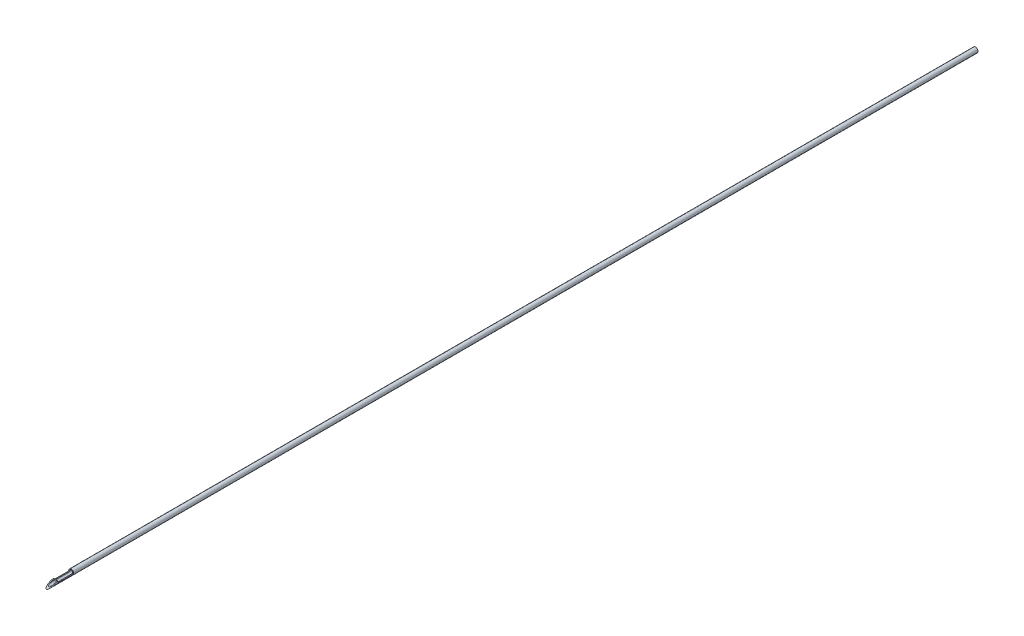
SolidWorks part; units mm, degrees
ref_plane "Front" through (0, 0, 0) normal (0, 0, 1) x (1, 0, 0)
ref_plane "Top" through (0, 0, 0) normal (0, 1, 0) x (1, 0, 0)
ref_plane "Right" through (0, 0, 0) normal (1, 0, 0) x (0, 0, -1)
sketch "Sketch1" plane through (0, 0, 0) normal (0, 0, 1) x (1, 0, 0)
  circle A0 centre (0, 0) radius 0.255
  circle A1 centre (0, 0) radius 0.405
  dimension "D1" = 0.51
  dimension "D2" = 0.81
extrude "Boss-Extrude1" add sketch "Sketch1" along normal blind 150
sketch "Sketch2" plane through (0, 0, 0) normal (1, 0, 0) x (0, 0, -1)
  line L0 (-150, -0.405) -> (0, -0.405) construction
  line L1 (-150, -0.405) -> (0, -0.405) construction
  line L2 (-150, 0.405) -> (-150, -0.405) construction
  line L3 (-150, 0.405) -> (-150, -0.405) construction
  line L4 (-150, -0.405) -> (-148.5149, 0.195)
  line L5 (-148.5149, 0.195) -> (-148.5149, -0.055)
  line L6 (-148.5149, -0.055) -> (-146.0149, -0.055)
  line L7 (-146.0149, -0.055) -> (-146.0149, 0.595)
  line L8 (-146.0149, 0.595) -> (-150.3, 0.595)
  line L9 (-150.3, 0.595) -> (-150.3, -0.405)
  line L10 (-150.3, -0.405) -> (-150, -0.405)
  line L11 (0, 0.255) -> (-150, 0.255) construction
  line L12 (0, 0.255) -> (-75, 0.255) construction
  dimension "D1" = 22
  dimension "D2" = 0.6
  dimension "D3" = 2.5
  dimension "D4" = 0.35
  dimension "D5" = 0.3
  dimension "D6" = 1
extrude "Cut-Extrude1" cut sketch "Sketch2" against normal mid plane 1
ref_axis "Axis-Tube21" through (0, 0, 149.6287) along (0, 0, -1)
